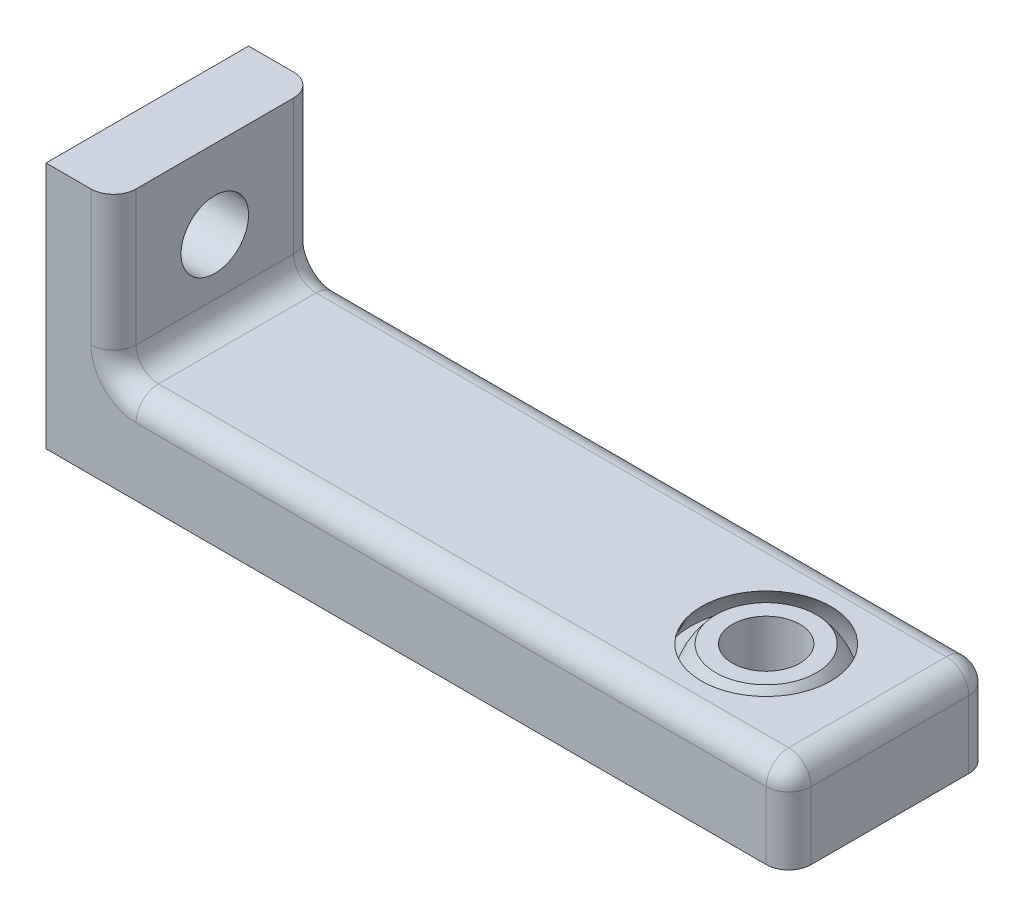
SolidWorks part; units mm, degrees
ref_plane "Front Plane" through (0, 0, 0) normal (0, 0, 1) x (1, 0, 0)
ref_plane "Top Plane" through (0, 0, 0) normal (0, 1, 0) x (1, 0, 0)
ref_plane "Right Plane" through (0, 0, 0) normal (1, 0, 0) x (0, 0, -1)
sketch "Sketch1" plane through (0, 0, 0) normal (0, 0, 1) x (1, 0, 0)
  line L0 (0, 0) -> (-6, 0)
  arc A0 (-6, 0) -> (0, 0) centre (-3, 0) cw
  dimension "D1" = 6
  dimension "D2" = 3
revolve "Revolve1" add sketch "Sketch1" angle 360 about L0
sketch "Sketch2" plane through (0, 0, 0) normal (0, 1, 0) x (1, 0, 0)
  circle A0 centre (-3, 0) radius 1.5
  dimension "D1" = 3
extrude "Cut-Extrude1" cut sketch "Sketch2" against normal blind 10 and the other way blind 10
sketch "Sketch4" plane through (0, 0, 0) normal (0, 1, 0) x (1, 0, 0)
  line L0 (-30.5, 0) -> (-19.7447, 0) construction
  line L1 (2.5, 4.5) -> (-30.5, 4.5)
  line L2 (2.5, 4.5) -> (2.5, -4.5)
  line L3 (2.5, -4.5) -> (-30.5, -4.5)
  line L4 (-30.5, 4.5) -> (-30.5, -4.5)
  line L5 (-7.5, 4.5) -> (-7.5, -4.5) construction
  circle A0 centre (-3, 0) radius 3.5 construction
  dimension "D4" = 4.5
  dimension "D1" = 9
  dimension "D2" = 0
  dimension "D3" = 5.5
  dimension "D5" = 23
extrude "Boss-Extrude1" add sketch "Sketch4" along normal blind 2 and the other way blind 2
sketch "Sketch5" plane through (0, 2, 0) normal (0, 1, 0) x (1, 0, 0)
  circle A0 centre (-3, 0) radius 1.5
extrude "Cut-Extrude2" cut sketch "Sketch5" against normal blind 10 and the other way blind 1.5
sketch "Sketch6" plane through (0, 0, 0) normal (0, 1, 0) x (1, 0, 0)
  line L0 (-3, 3.5) -> (-3, -3.5)
  arc A0 (-3, 3.5) -> (-3, -3.5) centre (-3, 0) ccw
revolve "Cut-Revolve1" cut sketch "Sketch6" angle 360 about L0
sketch "Sketch7" plane through (0, 0, 0) normal (0, 1, 0) x (1, 0, 0)
  line L0 (-3, 3) -> (-3, -3)
  arc A0 (-3, 3) -> (-3, -3) centre (-3, 0) ccw
  dimension "D1" = 6
revolve "Revolve2" add sketch "Sketch7" angle 360 about L0
sketch "Sketch8" plane through (0, 0, 0) normal (0, 1, 0) x (1, 0, 0)
  circle A0 centre (-3, 0) radius 1.5
  dimension "D1" = 3
extrude "Cut-Extrude3" cut sketch "Sketch8" against normal blind 10 and the other way blind 10
sketch "Sketch9" plane through (-30.5, 0, 0) normal (-1, 0, 0) x (0, 0, 1)
  line L1 (-4.5, 2) -> (4.4875, 2)
  line L2 (-4.5, 2) -> (-4.5, 2.7813)
  line L3 (-4.5, 2.7813) -> (4.4875, 2.7813)
  line L4 (4.4875, 2) -> (4.4875, 2.7813)
  line L5 (-4.5, -2) -> (4.4875, -2)
  line L6 (-4.5, -2) -> (-4.5, -3.2255)
  line L7 (-4.5, -3.2255) -> (4.4875, -3.2255)
  line L8 (4.4875, -2) -> (4.4875, -3.2255)
extrude "Cut-Extrude4" cut sketch "Sketch9" against normal blind 46
sketch "Sketch10" plane through (-30.5, 0, 0) normal (-1, 0, 0) x (0, 0, 1)
  line L1 (-2.75, 1) -> (2.75, 1)
  line L2 (-2.75, 1) -> (-2.75, -1)
  line L3 (-2.75, -1) -> (2.75, -1)
  line L4 (2.75, 1) -> (2.75, -1)
  line L5 (-2.75, 1) -> (2.75, -1) construction
  line L6 (-2.75, -1) -> (2.75, 1) construction
  point P0 (0, 0)
  dimension "D1" = 5.5
  dimension "D2" = 2
extrude "Cut-Extrude5" cut sketch "Sketch10" against normal blind 30
sketch "Sketch11" plane through (0, 2, 0) normal (0, 1, 0) x (1, 0, 0)
  line L0 (-30.5, -4.5) -> (2.5, -4.5) construction
  line L1 (-30.5, 4.5) -> (-27.5, 4.5)
  line L2 (-30.5, 4.5) -> (-30.5, -4.5)
  line L3 (-30.5, -4.5) -> (-27.5, -4.5)
  line L4 (-27.5, 4.5) -> (-27.5, -4.5)
  dimension "D1" = 3
extrude "Boss-Extrude2" add sketch "Sketch11" along normal blind 7
sketch "Sketch12" plane through (-27.5, 0, 0) normal (1, 0, 0) x (0, 0, -1)
  line L0 (-4.5, 9) -> (4.5, 9) construction
  circle A0 centre (0, 5.5) radius 1.5
  dimension "D1" = 3
  dimension "D2" = 3.5
extrude "Cut-Extrude6" cut sketch "Sketch12" against normal blind 7
fillet "Fillet1" radius 1 1 edges at (2.5, 0, -4.5)
fillet "Fillet2" radius 1 1 edges at (2.5, 0, 4.5)
fillet "Fillet3" radius 1 1 edges at (-27.5, 2, 0)
fillet "Fillet4" radius 1 9 edges at (-27.5, 6, 4.5) (-27.2071, 2.2929, 4.5) (-12.5, 2, 4.5) (2.2071, 2, 4.2071) (2.5, 2, 0) (2.2071, 2, -4.2071) (-27.5, 6, -4.5) (-27.2071, 2.2929, -4.5) (-12.5, 2, -4.5)
